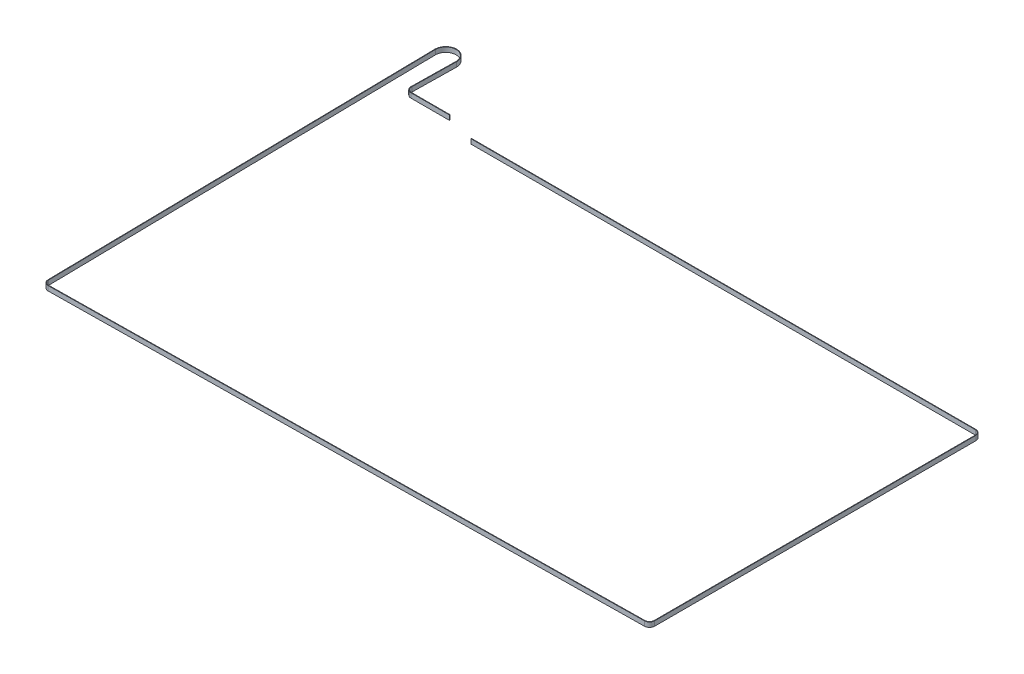
SolidWorks part; units mm, degrees
material "BUTYL"
ref_plane "Front Plane" through (0, 0, 0) normal (0, 0, 1) x (1, 0, 0)
ref_plane "Top Plane" through (0, 0, 0) normal (0, 1, 0) x (1, 0, 0)
ref_plane "Right Plane" through (0, 0, 0) normal (1, 0, 0) x (0, 0, -1)
ref_plane "Plane1" through (0, 12.5, 0) normal (0, -1, 0) x (-1, 0, 0)
sketch "Sketch2" plane through (0, 12.5, 0) normal (0, -1, 0) x (-1, 0, 0)
  line L0 (-67.9386, -63.0886) -> (-19, -63.0886)
  line L1 (-67.9386, -62.5886) -> (-67.9386, -63.5886) construction
  line L2 (-12.9754, -55.8332) -> (-12.25, -56.6071) construction
  line L3 (-12.6127, -56.2202) -> (-13.4983, -0.2134)
  line L4 (13.5, 0) -> (5.575, -501.15)
  line L6 (-0.675, -507.4) -> (-751, -497.4)
  line L7 (-757.25, -491.15) -> (-757.25, -81.5886)
  line L8 (-751, -75.3386) -> (-107.9386, -75.5886)
  arc A0 (-19, -63.0886) -> (-12.6127, -56.2202) centre (-19, -56.6844) ccw
  arc A1 (-13.4983, -0.2134) -> (13.5, 0) centre (0, 0) cw
  arc A2 (5.575, -501.15) -> (-0.675, -507.4) centre (-0.675, -501.15) cw
  arc A3 (-751, -497.4) -> (-757.25, -491.15) centre (-751, -491.15) cw
  arc A4 (-757.25, -81.5886) -> (-751, -75.3386) centre (-751, -81.5886) cw
  circle A5 centre (-751, -81.5886) radius 6.25 construction
  circle A6 centre (-0.675, -501.15) radius 6.25 construction
  circle A8 centre (-751, -491.15) radius 6.25 construction
  circle A13 centre (0, 0) radius 13.5 construction
  arc A14 (3.5, 0) -> (-3.5, 0) centre (0, 0) ccw construction
ref_plane "Plane2" through (-13.5, 12.5, 0) normal (0.0158, 0, 0.9999) x (0.9999, 0, -0.0158)
sketch "Sketch5" plane through (-13.5, 12.5, 0) normal (0.0158, 0, 0.9999) x (0.9999, 0, -0.0158)
  line L0 (-0.0008, 0) -> (6.1504, 0) construction
  line L1 (0.335, -3) -> (-0.335, -3)
  line L2 (0.335, -3) -> (0.335, 3)
  line L3 (0.335, 3) -> (-0.335, 3)
  line L4 (-0.335, -3) -> (-0.335, 3)
  line L5 (0.335, -3) -> (-0.335, 3) construction
  line L6 (0.335, 3) -> (-0.335, -3) construction
  point P0 (0, 0)
  dimension "D1" = 6
  dimension "D2" = 0.67
sweep "Sweep3" add profiles "Sketch5" path "Sketch2"
ref_plane "Plane3" through (0, 3.5, 0) normal (0, 1, 0) x (1, 0, 0)
sketch "Sketch9" plane through (0, 3.5, 0) normal (0, 1, 0) x (1, 0, 0)
  line L0 (499.575, -465.15) -> (502, 0)
  line L1 (486, 0) -> (479.25, -56.5886)
  line L2 (475, -60.8386) -> (107.9386, -63.5886)
  line L3 (493.2924, -471.3999) -> (19, -461.4)
  line L5 (12.75, -455.15) -> (14.75, -280.0923)
  line L6 (232.1882, -274.0923) -> (19, -275.8423)
  circle A0 centre (769.325, -501.15) radius 6.25 construction
  arc A1 (502, 0) -> (486, 0) centre (494, 0) ccw
  arc A2 (499.575, -465.15) -> (493.2924, -471.3999) centre (493.2924, -465.1172) cw
  circle A3 centre (475, -56.5886) radius 4.25 construction
  arc A4 (479.25, -56.5886) -> (475, -60.8386) centre (475, -56.5886) cw
  circle A5 centre (19, -491.15) radius 6.25 construction
  arc A6 (19, -461.4) -> (12.75, -455.15) centre (19.1346, -455.0154) cw
  circle A7 centre (770, 0) radius 8 construction
  circle A8 centre (19, -81.5886) radius 4.25 construction
  arc A9 (19, -275.8423) -> (14.75, -280.0923) centre (19.0352, -280.1275) ccw
ref_plane "Plane4" through (499.575, 3.5, 465.15) normal (0.0052, 0, -1) x (-1, 0, -0.0052)
sketch "Sketch10" plane through (499.575, 3.5, 465.15) normal (0.0052, 0, -1) x (-1, 0, -0.0052)
  line L0 (6.2499, 0) -> (0, 0) construction
  line L1 (0.335, -3) -> (-0.335, -3)
  line L2 (0.335, -3) -> (0.335, 3)
  line L3 (0.335, 3) -> (-0.335, 3)
  line L4 (-0.335, -3) -> (-0.335, 3)
  line L5 (0.335, -3) -> (-0.335, 3) construction
  line L6 (0.335, 3) -> (-0.335, -3) construction
  point P0 (0, 0)
  dimension "D1" = 6
  dimension "D2" = 0.67
sweep "Sweep4" add profiles "Sketch10" path "Sketch9" rebuild error yes
